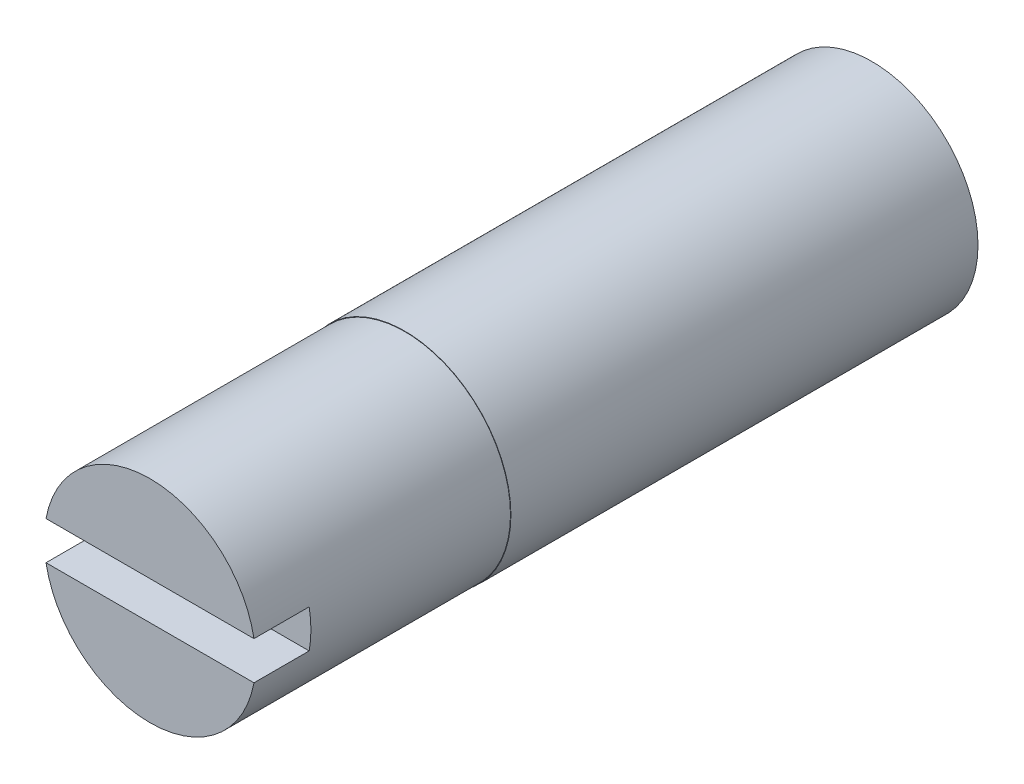
SolidWorks part; units mm, degrees
other "標示1"
sketch "草圖14" plane through (-2.5, 2.5, 3.5) normal (-0.7678, 0.631, 0.1112) x (-0.6334, -0.7736, 0.0168)
other "標示2"
sketch "草圖15" plane through (-2.5, -2.5, 3) normal (-0.8992, -0.1971, 0.3907) x (0.3045, -0.923, 0.2352)
other "標示3"
sketch "草圖16" plane through (-2.5, -2.5, -11) normal (-0.6524, -0.7559, -0.0546) x (0.7385, -0.6503, 0.1783)
ref_plane "前基準面" through (0, 0, 0) normal (0, 0, 1) x (1, 0, 0)
ref_plane "上基準面" through (0, 0, 0) normal (0, 1, 0) x (1, 0, 0)
ref_plane "右基準面" through (0, 0, 0) normal (1, 0, 0) x (0, 0, -1)
sketch "草圖1" plane through (0, 0, 0) normal (0, 0, 1) x (1, 0, 0)
  circle A0 centre (0, 0) radius 2.49
  dimension "D1" = 4.98
extrude "填料-伸長1" add sketch "草圖1" along normal blind 6
sketch "草圖8" plane through (0, 0, 6) normal (0, 0, 1) x (1, 0, 0)
  line L0 (0, 0) -> (2.5, 0)
  line L1 (2.5, -0.45) -> (2.5, 0.45)
  line L6 (-2.5, -0.45) -> (2.5, -0.45)
  line L7 (2.5, 0.45) -> (-2.5, 0.45)
  line L8 (0, 2.49) -> (0, -2.49)
  line L9 (-2.5, -0.45) -> (-2.5, 0.45)
  circle A0 centre (0, 0) radius 2.49 construction
  point P13 (0, -0.45)
  point P14 (0, 0.45)
  dimension "D1" = 0.45
  dimension "D2" = 2.5
extrude "除料-伸長2" cut sketch "草圖8" against normal blind 1.3 contours L0 L1 | L0 L1 | L6 L1 L7 L9 region at (1.25, 0.225, 6) region at (1.25, -0.225, 6)
sketch "草圖9" plane through (0, 0, 0) normal (0, 0, -1) x (-1, 0, 0)
  circle A0 centre (0, 0) radius 2.5
  dimension "D1" = 5
extrude "填料-伸長2" add sketch "草圖9" along normal blind 11
